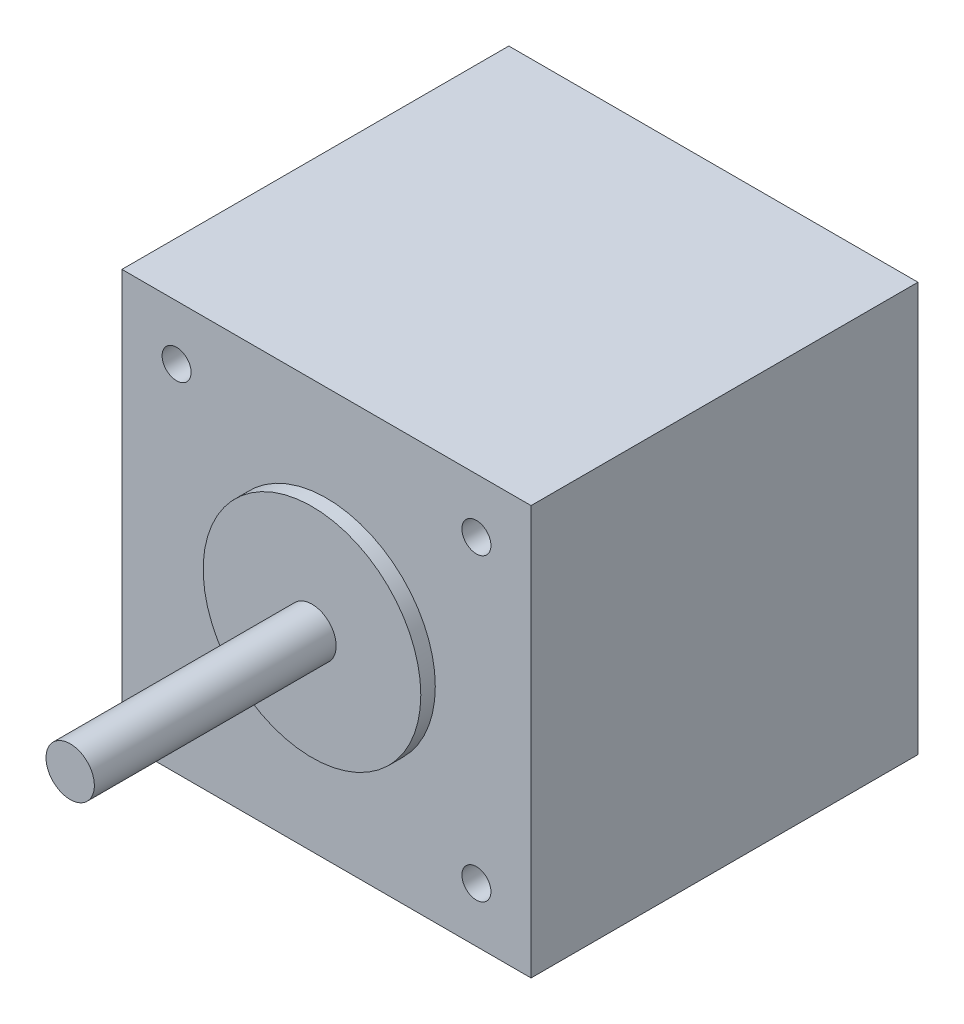
SolidWorks part; units mm, degrees
ref_plane "Front Plane" through (0, 0, 0) normal (0, 0, 1) x (1, 0, 0)
ref_plane "Top Plane" through (0, 0, 0) normal (0, 1, 0) x (1, 0, 0)
ref_plane "Right Plane" through (0, 0, 0) normal (1, 0, 0) x (0, 0, -1)
sketch "Sketch1" plane through (0, 0, 0) normal (0, 0, 1) x (1, 0, 0)
  line L1 (-21.15, -21.15) -> (21.15, -21.15)
  line L2 (-21.15, -21.15) -> (-21.15, 21.15)
  line L3 (-21.15, 21.15) -> (21.15, 21.15)
  line L4 (21.15, -21.15) -> (21.15, 21.15)
  line L5 (-21.15, -21.15) -> (21.15, 21.15) construction
  line L6 (-21.15, 21.15) -> (21.15, -21.15) construction
  circle A0 centre (15.5, 15.5) radius 1.5
  circle A1 centre (15.5, -15.5) radius 1.5
  circle A2 centre (-15.5, -15.5) radius 1.5
  circle A3 centre (-15.5, 15.5) radius 1.5
  circle A4 centre (0, 0) radius 11.25
  circle A5 centre (0, 0) radius 2.5
  point P0 (0, 0)
  point P17 (0, 0)
  dimension "D4" = 3
  dimension "D5" = 22.5
  dimension "D6" = 5
  dimension "D1" = 42.3
  dimension "D3" = 31
  dimension "D2" = 4
extrude "Boss-Extrude1" add sketch "Sketch1" against normal blind 40 contours L2 L3 L4 L1
extrude "Cut-Extrude1" cut sketch "Sketch1<3>" against normal blind 5 contours A2 | A0 | A1 | A3 region at (15.5, 15.5, 0) region at (15.5, -15.5, 0) region at (-15.5, -15.5, 0)
sketch "Sketch1<3>" plane through (0, 0, 0) normal (0, 0, 1) x (1, 0, 0) same geometry as "Sketch1"
extrude "Boss-Extrude2" add sketch "Sketch1<4>" along normal blind 1.5 contours A4 A5 region at (-10.9318, 0, 0)
sketch "Sketch1<4>" plane through (0, 0, 0) normal (0, 0, 1) x (1, 0, 0) same geometry as "Sketch1"
extrude "Boss-Extrude3" add sketch "Sketch1<5>" along normal blind 25 and the other way up to surface from surface contours A5 region at (0, 0, 0) other way up to face at (11.25, 0, 0) starting at face at (2.5, 0, 1.5)
sketch "Sketch1<5>" plane through (0, 0, 0) normal (0, 0, 1) x (1, 0, 0) same geometry as "Sketch1"
sketch "Sketch3" plane through (0, -21.15, 0) normal (0, -1, 0) x (1, 0, 0)
  line L0 (-21.15, -40) -> (21.15, -40) construction
  line L1 (-8.5, -40) -> (8.5, -40)
  line L2 (-8.5, -40) -> (-8.5, -31)
  line L3 (-8.5, -31) -> (8.5, -31)
  line L4 (8.5, -40) -> (8.5, -31)
  line L5 (0, 0) -> (0, -40) construction
  line L6 (-21.15, 0) -> (21.15, 0) construction
  dimension "D1" = 17
  dimension "D2" = 9
extrude "Boss-Extrude4" add sketch "Sketch3" along normal blind 5
ref_axis "Axis1" through (0, 0, 1.5) along (0, 0, 1)
equation "\"ShaftLength\"= 25"
equation "\"D1@Boss-Extrude3\"= \"ShaftLength\""
